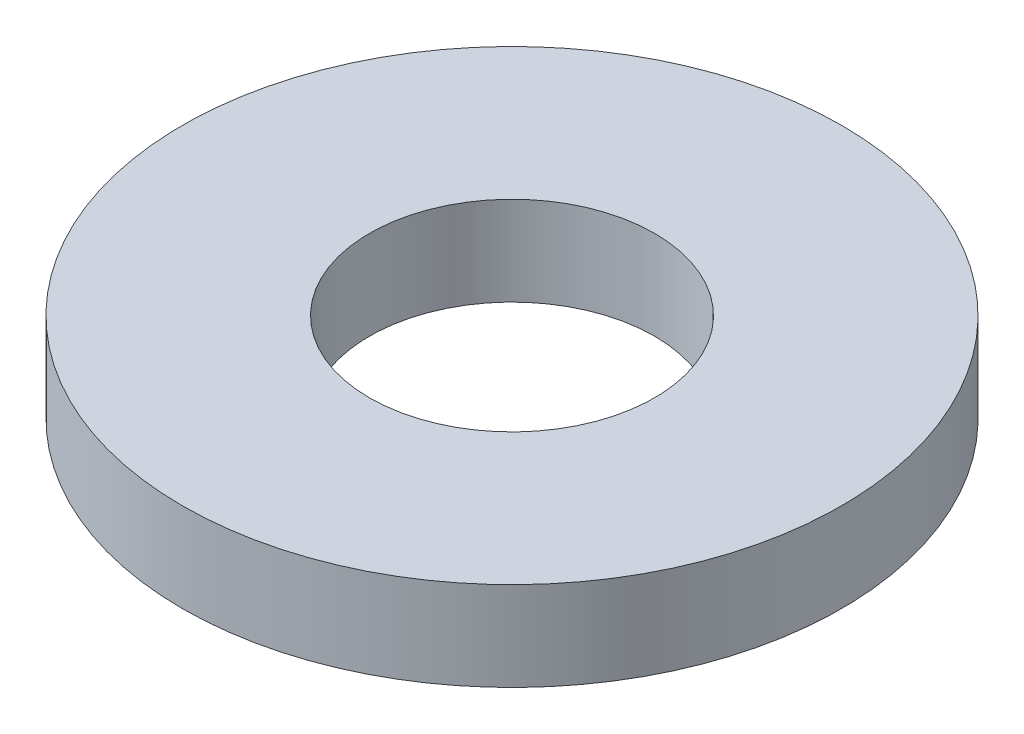
SolidWorks part; units mm, degrees
ref_plane "Front Plane" through (0, 0, 0) normal (0, 0, 1) x (1, 0, 0)
ref_plane "Top Plane" through (0, 0, 0) normal (0, 1, 0) x (1, 0, 0)
ref_plane "Right Plane" through (0, 0, 0) normal (1, 0, 0) x (0, 0, -1)
sketch "Sketch1" plane through (0, 0, 0) normal (0, 1, 0) x (1, 0, 0)
  circle A0 centre (0, 0) radius 92.5
  dimension "FLANGE_OD" = 185
extrude "Boss-Extrude1" add sketch "Sketch1" along normal blind 25
sketch "Sketch2" plane through (0, 0, 0) normal (0, 1, 0) x (1, 0, 0)
  circle A0 centre (0, 0) radius 40
  dimension "BORE_D" = 80
extrude "Cut-Extrude1" cut sketch "Sketch2" along normal through all
sketch "Sketch3" plane through (0, 25, 0) normal (0, 1, 0) x (1, 0, 0)
  circle A0 centre (0, 0) radius 29.7483 construction
  circle A1 centre (-29.7483, 0) radius 7.0421
  dimension "BOLT_D" = 14.0842
  dimension "BOLT_PCD" = 59.4965
extrude "Cut-Extrude2" cut sketch "Sketch3" against normal blind 16.8412 rebuild error yes
pattern_circular "CirPattern1" count 5 over 360 rebuild error yes
